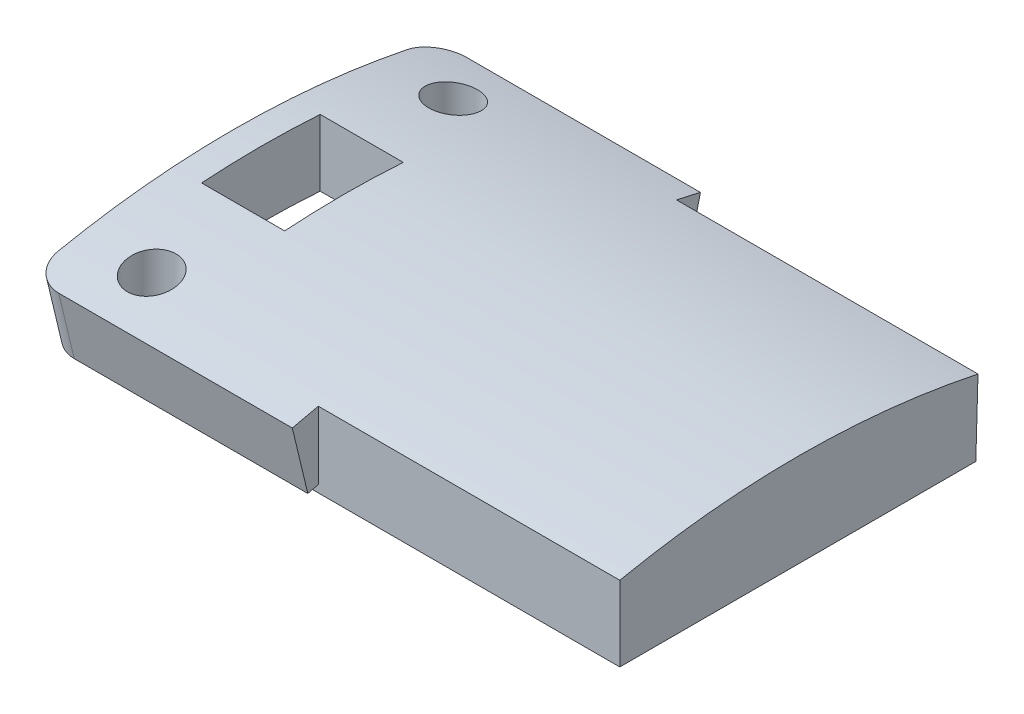
SolidWorks part; units mm, degrees
ref_plane "Front Plane" through (0, 0, 0) normal (0, 0, 1) x (1, 0, 0)
ref_plane "Top Plane" through (0, 0, 0) normal (0, 1, 0) x (1, 0, 0)
ref_plane "Right Plane" through (0, 0, 0) normal (1, 0, 0) x (0, 0, -1)
sketch "Sketch1" plane through (0, 0, 0) normal (0, 0, 1) x (1, 0, 0)
  line L0 (21.581, -73.66) -> (-66.7143, -73.66) construction
  line L1 (-11.1125, -5.588) -> (11.1125, -5.588)
  line L2 (11.1125, -5.588) -> (11.1125, 0)
  line L3 (11.1125, 0) -> (-11.1125, 0)
  line L4 (-11.1125, 0) -> (-11.1125, -5.588)
  dimension "D1" = 73.66
  dimension "D2" = 5.588
  dimension "D3" = 22.225
revolve "Revolve1" add sketch "Sketch1" angle 27 mid plane about L0
sketch "Sketch2" plane through (0, 0, 0) normal (0, 1, 0) x (1, 0, 0)
  line L0 (-11.1125, 17.1956) -> (-11.1125, -17.1956) construction
  line L1 (-1.7313, -5) -> (-8.7312, -5)
  line L2 (-1.7313, -5) -> (-1.7313, 5)
  line L3 (-1.7313, 5) -> (-8.7312, 5)
  line L4 (-8.7312, -5) -> (-8.7312, 5)
  line L5 (-1.7313, -5) -> (-8.7312, 5) construction
  line L6 (-1.7313, 5) -> (-8.7312, -5) construction
  line L7 (11.1125, -17.1956) -> (11.1125, 17.1956) construction
  line L8 (-11.1125, 17.1956) -> (-11.1125, -17.1956)
  line L9 (11.1125, -17.1956) -> (11.1125, 17.1956)
  line L10 (-11.1125, 0) -> (11.1125, 0) construction
  circle A1 centre (-5.2313, 12.7) radius 2.05
  circle A2 centre (-5.2313, -12.7) radius 2.05
  point P0 (-5.2313, 0)
  dimension "D6" = 4.1
  dimension "D1" = 10
  dimension "D2" = 7
  dimension "D4" = 2.3813
  dimension "D7" = 12.7
extrude "Cut-Extrude1" cut sketch "Sketch2" against normal through all contours L4 L1 L2 L3 | A1 | A2 region at (-5.2313, 0, 0)
ref_plane "Plane1" through (3.3487, 0, 0) normal (-1, 0, 0) x (0, 0, 1)
shell "Shell2" [suppressed] thickness 1.905
sketch "Sketch5" [suppressed] plane through (9.2075, 0, 0) normal (-1, 0, 0) x (0, 0, 1)
  line L2 (3.383, -0.1219) -> (3.383, -5.7264)
  line L6 (8.8642, -6.548) -> (10.3118, -1.1454)
  line L7 (8.8642, -6.548) -> (10.3118, -1.1454)
  line L8 (3.383, -0.1219) -> (3.383, -5.7264)
  arc A2 (8.8642, -6.548) -> (3.383, -5.7264) centre (0, -46.99) ccw
  arc A3 (8.8642, -6.548) -> (3.383, -5.7264) centre (0, -46.99) ccw
  arc A6 (10.3118, -1.1454) -> (3.383, -0.1219) centre (0, -46.99) ccw
  arc A7 (10.3118, -1.1454) -> (3.383, -0.1219) centre (0, -46.99) ccw
  dimension "D1" = 0
extrude "Cut-Extrude2" [suppressed] cut sketch "Sketch5" against normal through all
fillet "Fillet1" [suppressed] radius 2.54
fillet "Fillet2" radius 2.54 2 edges at (-11.1125, -4.752, -16.5433) (-11.1125, -4.752, 16.5433)
sketch "Sketch8" plane through (11.1125, 0, 0) normal (1, 0, 0) x (0, 0, -1)
  line L2 (-15, -7.874) -> (15, -7.874)
  line L5 (-15, -7.874) -> (-15, -1.5435)
  line L6 (15, -7.874) -> (15.1846, -1.5821)
  arc A0 (17.1956, -2.0352) -> (-17.1956, -2.0352) centre (0, -73.66) ccw construction
  arc A1 (15.1846, -1.5821) -> (-15, -1.5435) centre (0, -73.66) ccw
  point P0 (0, -7.874)
  dimension "D1" = 30
  dimension "D2" = 7.874
extrude "Boss-Extrude2" add sketch "Sketch8" along normal blind 25.4 and the other way blind 1.27
hole_wizard "#24 (0.152) Diameter Hole1" positions "Sketch9" profile "Sketch10" hole size "#24" standard "ANSI Inch"
sketch "Sketch9" plane through (0, -7.874, 0) normal (0, -1, 0) x (-1, 0, 0)
  line L2 (1.7313, -5) -> (1.7313, 5) construction
  point P0 (-32.2687, 11.5)
  point P2 (-32.2687, -11.5)
  dimension "D1" = 23
  dimension "D2" = 11.5
  dimension "D3" = 34
sketch "Sketch10" plane through (32.2687, -7.874, -11.5) normal (1, 0, 0) x (0, 0, -1)
  line L0 (0, 0) -> (0, 4.5599)
  line L1 (0, 4.5599) -> (1.9304, 3.4)
  line L2 (1.9304, 3.4) -> (1.9304, 0)
  line L5 (1.9304, 0) -> (0, 0)
  line L10 (0, 4.5599) -> (-1.9304, 3.4) construction
  line L11 (0, -6.35) -> (0, 107.95) construction
  dimension "Hole Dia." = 3.8608
  dimension "Hole Depth" = 3.4
  dimension "Drill Angle" = 118
sketch "Sketch12" plane through (9.8425, 0, 0) normal (-1, 0, 0) x (0, 0, 1)
  circle A0 centre (-23.333, -17.3422) radius 9
  point P7 (-0.7963, -74.8918)
  dimension "D1" = 18
extrude "Cut-Extrude3" [suppressed] cut sketch "Sketch12" against normal blind 24
sketch "Sketch13" [suppressed] plane through (33.8425, 0, 0) normal (-1, 0, 0) x (0, 0, 1)
  circle A0 centre (-23.333, -17.3422) radius 9
  arc A1 (-19.6767, -9.1184) -> (-31.734, -14.1138) centre (-23.333, -17.3422) ccw construction
extrude "Boss-Extrude3" [suppressed] add sketch "Sketch13" against normal up to surface (2.67 mm away) up to face at (36.5125, -4.3277, -0.0467)
fillet "Fillet3" [suppressed] radius 2.54
sketch "Sketch14" [suppressed] plane through (9.8425, 0, 0) normal (-1, 0, 0) x (0, 0, 1)
  line L0 (-40.4766, -12.1178) -> (-37.0776, -17.2858)
  line L1 (-15, -7.874) -> (-17.2354, -2.0448)
  arc A0 (-13.4235, -1.2334) -> (-40.4766, -12.1178) centre (0, -73.66) ccw construction
  arc A1 (-40.4766, -12.1178) -> (-17.2354, -2.0448) centre (0, -73.66) cw
  arc A2 (-37.0776, -17.2858) -> (-31.734, -14.1138) centre (0, -73.66) cw
  arc A3 (-31.734, -14.1138) -> (-37.0776, -17.2858) centre (0, -73.66) ccw construction
  arc A4 (-31.734, -14.1138) -> (-19.6767, -9.1184) centre (-23.333, -17.3422) cw
  arc A5 (-19.6767, -9.1184) -> (-31.734, -14.1138) centre (-23.333, -17.3422) ccw construction
  arc A6 (-19.6767, -9.1184) -> (-15, -7.874) centre (0, -73.66) cw
  arc A7 (-15, -7.874) -> (-19.6767, -9.1184) centre (0, -73.66) ccw construction
extrude "Boss-Extrude4" [suppressed] add sketch "Sketch14" along normal blind 20
sketch "Sketch16" [suppressed] plane through (33.8425, 0, 0) normal (-1, 0, 0) x (0, 0, 1)
  line L0 (-27.4395, -19.0436) -> (-24.4441, -26.2734)
  line L1 (-19.2265, -15.6408) -> (-16.2311, -22.8706)
  line L2 (-23.333, -17.3422) -> (0, -73.66) construction
  arc A0 (-19.2265, -15.6408) -> (-27.4395, -19.0436) centre (-23.333, -17.3422) ccw
  circle A1 centre (-23.333, -17.3422) radius 9 construction
  arc A2 (-16.2311, -22.8706) -> (-24.4441, -26.2734) centre (-23.333, -17.3422) cw
  circle A3 centre (0, -73.66) radius 73.66 construction
  arc A4 (-17.2354, -2.0448) -> (-40.4766, -12.1178) centre (0, -73.66) ccw construction
  dimension "D1" = 8.89
extrude "Cut-Extrude4" [suppressed] cut sketch "Sketch16" against normal through all
fillet "Fillet5" [suppressed] radius 0.254
equation "\"Mid_Coupler_ID\"= 3.7"
equation "\"Thiccness\"= 5.5mm"
equation "\"Bracket_Angle\"= 27"
equation "\"D1@Revolve1\"=\"Bracket_Angle\""
equation "\"Cam_Slot_Width\"= 10mm"
equation "\"Cam_Slot_Length\"= 7mm"
equation "\"D1@Sketch2\"=\"Cam_Slot_Width\""
equation "\"D2@Sketch2\"=\"Cam_Slot_Length\""
equation "\"Screw_Angle\"= 12.5deg"
equation "\"M3_Insert_OD\"= 4.1mm"
equation "\"Length\"= ( 7 / 8 ) * 1in"
equation "\"D3@Sketch1\"=\"Length\""
equation "\"Mid_Tube_Length\"= 1in"
equation "\"Bodytube_OD\" = 6.17in"
equation "\"Bodytube_ID\" = 5.998in"
equation "\"Camera_Cutout_Width\"=10mm"
equation "\"Camera_Cutout_Height\"=7mm"
equation "\"Fwd_Tube_Length\" = 38.5in"
equation "\"BKHD_Screw_Diam\"= 3.5mm"
equation "\"Fwd_BKHD_From_Top\" = 18in"
equation "\"Shear_Screw_Diameter\" = 0.086in"
equation "\"Shear_Screw_Coupler_Location\" = 4.5in"
equation "\"Motor_OD\" = 4in"
equation "\"Mid_Coupler_Length\" = 13in"
equation "\"Aft_Section_Length\"= 36in"
equation "\"AB_Coupler_OD_Length\"= 1in"
equation "\"AB_Coupling_Section_Length\"= 0.375in"
equation "\"AB_Coupler_Length\"= \"AB_Coupler_OD_Length\" + \"AB_Coupling_Section_Length\" * 2"
equation "\"Cutout_Angle\" = 80"
equation "\"AB_Paddle_Height\" = 0.375in"
equation "\"AB_Coupler_Num_Screws\"= 4"
equation "\"AB_BKHD_Thickness\" = 0.375in"
equation "\"AB_Mount_From_Bottom\" = 23.175in"
equation "\"Num_Cutouts\" = 3"
equation "\"AB_Coupler_OD\"= 6.17in"
equation "\"AB_Coupler_ID\"= 5.75in"
equation "\"AB_Coupler_Surface_Diameter\"= 5.998in"
equation "\"AB_Coupling_Screw_Diameter\"= 0.15748in"
equation "\"AB_Central_Bushing_Length\" = .4724in"
equation "\"Lead_Screw_Dist\" = 3.4in"
equation "\"Lead_Screw_Diam\" = 0.386in"
equation "\"Lead_Screw_Length\" = (\"Mid_Coupler_Length\" + 2*0.375in + 2*.75in)"
equation "\"Paddle_Pin_Offset\" = .25in"
equation "\"Paddle_Pin_Radius\" = 2.25in"
equation "\"SS_Paddle_Pin_Radius\" = 2.25*0.66in"
equation "\"Paddle_Gear_OD\" = 3.2in"
equation "\"Drive_Gear_OD\" = 1.7in"
equation "\"Fin_Thickness\"= .118in"
equation "\"Guiderail_Cutout_Diameter\"= 1.5in"
equation "\"DB9_Hole_Dist\" = 25mm"
equation "\"DB9_Relief_Width\" = 0.47in"
equation "\"DB9_Relief_Hole_Offset\" = 0.09in"
equation "\"Airbrakes_Wire_Hole_Dia\" = .25in"
equation "\"Airbrakes_Wire_Hole_Dist\" = 1.1in"
equation "\"Servo_Gear_Offset\" = 0.5in"
equation "\"FWD_Shear_Screw_Dist\" = 1.5in"
equation "\"Camera_Screw_Dia\" = 0.216535"
equation "\"Camera_Hole_Angle\" = atn ( 2 / 3 * tan ( 12.5deg ) )"
equation "\"Coupler_OD\" = 5.998"
equation "\"Coupler_ID\" = 5.8"
equation "\"D1@Sketch3\"=\"Camera_Hole_Angle\"/2"
equation "\"D2@Sketch3\"=2*\"Thiccness\""
equation "\"D3@Sketch3\"=\"M3_Insert_OD\"/2"
